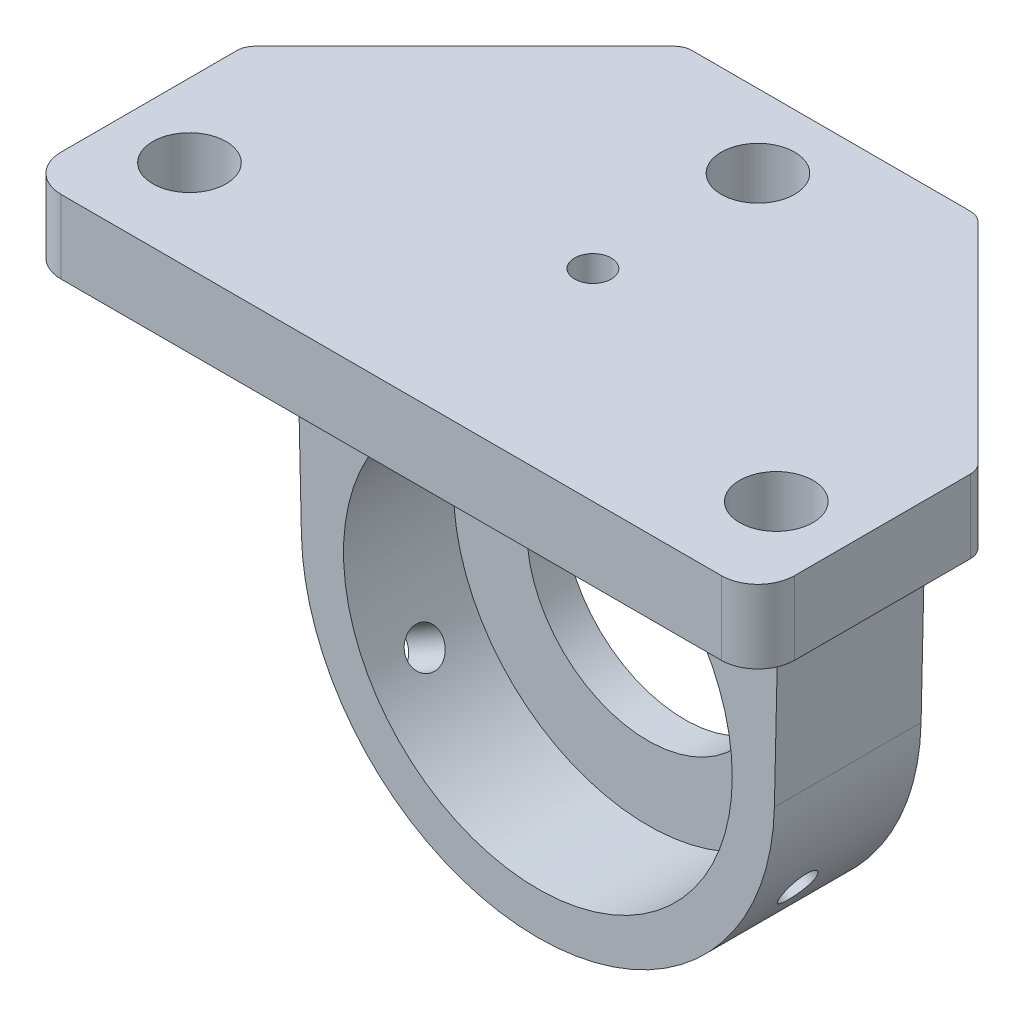
SolidWorks part; units mm, degrees
material "Delrin 2700 NC010, Low Viscosity Acetal Copolymer (SS)"
ref_plane "Front Plane" through (0, 0, 0) normal (0, 0, 1) x (1, 0, 0)
ref_plane "Top Plane" through (0, 0, 0) normal (0, 1, 0) x (1, 0, 0)
ref_plane "Right Plane" through (0, 0, 0) normal (1, 0, 0) x (0, 0, -1)
sketch "Sketch1" plane through (0, 0, 0) normal (0, 1, 0) x (1, 0, 0)
  line L1 (-57.15, 38.1) -> (57.15, 38.1)
  line L2 (-63.5, 31.75) -> (-63.5, -31.75)
  line L3 (-57.15, -38.1) -> (57.15, -38.1)
  line L4 (63.5, 31.75) -> (63.5, -31.75)
  line L5 (-63.5, 38.1) -> (63.5, -38.1) construction
  line L6 (-63.5, -38.1) -> (63.5, 38.1) construction
  arc A0 (57.15, -38.1) -> (63.5, -31.75) centre (57.15, -31.75) ccw
  arc A1 (57.15, 38.1) -> (63.5, 31.75) centre (57.15, 31.75) cw
  arc A2 (-57.15, 38.1) -> (-63.5, 31.75) centre (-57.15, 31.75) ccw
  arc A3 (-63.5, -31.75) -> (-57.15, -38.1) centre (-57.15, -31.75) ccw
  point P0 (0, 0)
  dimension "D3" = 6.35
  dimension "D1" = 76.2
  dimension "D2" = 127
extrude "Boss-Extrude1" add sketch "Sketch1" against normal blind 12.7
sketch "Sketch3" plane through (0, -12.7, 0) normal (0, -1, 0) x (1, 0, 0)
  line L0 (-63.5, -31.75) -> (-63.5, 31.75) construction
  line L1 (-57.15, 38.1) -> (57.15, 38.1) construction
  line L2 (0, 38.1) -> (0, -38.1) construction
  line L3 (57.15, -38.1) -> (-57.15, -38.1) construction
  line L4 (-63.5, 0) -> (63.5, 0) construction
  line L5 (63.5, 31.75) -> (63.5, -31.75) construction
  circle A0 centre (-50.8, 22.225) radius 6.35
  circle A1 centre (50.8, 22.225) radius 6.35
  circle A4 centre (0, -25.4) radius 6.35
  dimension "D1" = 12.7
  dimension "D4" = 12.7
  dimension "D2" = 12.7
  dimension "D3" = 15.875
extrude "Cut-Extrude1" cut sketch "Sketch3" against normal through all
sketch "Sketch2" plane through (0, 0, 0) normal (0, 0, 1) x (1, 0, 0)
  line L0 (0, 0) -> (0, -54.61) construction
  line L1 (-41.91, -12.7) -> (-40.9472, -55.5305)
  line L2 (-57.15, -12.7) -> (57.15, -12.7) construction
  line L3 (41.91, -12.7) -> (40.9472, -55.5305)
  line L4 (-63.5, -12.7) -> (-63.5, 0) construction
  line L5 (63.5, -12.7) -> (63.5, 0) construction
  line L6 (-41.91, -12.7) -> (41.91, -12.7)
  circle A0 centre (0, -54.61) radius 33.3375 construction
  circle A1 centre (0, -54.61) radius 19.05 construction
  arc A2 (-40.9472, -55.5305) -> (40.9472, -55.5305) centre (0, -54.61) ccw
  circle A4 centre (0, -54.61) radius 40.9575 construction
  point P18 (35.56, -54.61)
  dimension "D3" = 38.1
  dimension "D2" = 66.675
  dimension "D1" = 54.61
  dimension "D5" = 21.59
  dimension "D6" = 21.59
  dimension "D4" = 7.62
extrude "Boss-Extrude2" add sketch "Sketch2" along normal mid plane 25.4
sketch "Bearing Reference Geometry" plane through (0, 0, 12.7) normal (0, 0, 1) x (1, 0, 0)
  circle A0 centre (0, -54.61) radius 33.3375
  circle A1 centre (0, -54.61) radius 19.05
  arc A3 (-40.9472, -55.5305) -> (40.9472, -55.5305) centre (0, -54.61) ccw construction
  point P3 (0, -52.9618)
  dimension "D2" = 38.1
  dimension "D1" = 66.675
sketch "Sketch5" plane through (0, 0, 12.7) normal (0, 0, 1) x (1, 0, 0)
  circle A0 centre (0, -54.61) radius 33.655
  dimension "D1" = 67.31
extrude "Cut-Extrude2" cut sketch "Sketch5" against normal through all
sketch "Sketch6" plane through (0, 0, -12.7) normal (0, 0, -1) x (-1, 0, 0)
  circle A0 centre (0, -54.61) radius 33.655 construction
  circle A1 centre (0, -54.61) radius 33.655
  circle A2 centre (0, -54.61) radius 20.955
  dimension "D1" = 12.7
extrude "Boss-Extrude3" add sketch "Sketch6" against normal blind 6.35
ref_axis "Axis1" through (0, -54.61, -6.35) along (0, 0, 1)
sketch "Sketch7" plane through (0, 0, 0) normal (0, 1, 0) x (1, 0, 0)
  line L0 (-33.655, 6.35) -> (33.655, 6.35) construction
  line L1 (-33.655, 6.35) -> (33.655, 6.35) construction
  line L2 (-33.655, -12.7) -> (33.655, -12.7) construction
  line L3 (-33.655, -12.7) -> (33.655, -12.7) construction
  line L4 (-33.655, -3.175) -> (33.655, -3.175) construction
  circle A0 centre (0, -3.175) radius 3.175
  point P3 (0, 0)
  point P10 (-42.5215, -3.175)
  point P11 (5.9089, -3.175)
  point P12 (0, 0)
  dimension "D1" = 6.35
extrude "Cut-Extrude3" cut sketch "Sketch7" against normal up to next
pattern_circular "CirPattern1" count 3 over 360 about axis through (0, -54.61, 12.7) along (0, 0, 1) of "Cut-Extrude3"
sketch "Sketch8" plane through (0, -12.7, 0) normal (0, -1, 0) x (1, 0, 0)
  line L0 (-63.5, 0) -> (-25.4, -38.1)
  line L1 (-63.5, -31.75) -> (-63.5, 31.75) construction
  line L2 (57.15, -38.1) -> (-57.15, -38.1) construction
  line L3 (0, 38.1) -> (0, -38.1) construction
  line L4 (-57.15, 38.1) -> (57.15, 38.1) construction
  line L5 (57.15, -38.1) -> (25.4, -38.1)
  line L6 (-63.5, -31.75) -> (-63.5, 0)
  line L7 (63.5, 31.75) -> (63.5, -31.75) construction
  line L8 (63.5, 0) -> (63.5, -31.75)
  line L9 (63.5, 0) -> (25.4, -38.1)
  line L10 (-25.4, -38.1) -> (-57.15, -38.1)
  arc A0 (-63.5, -31.75) -> (-57.15, -38.1) centre (-57.15, -31.75) ccw construction
  arc A1 (-63.5, -31.75) -> (-57.15, -38.1) centre (-57.15, -31.75) ccw
  arc A2 (57.15, -38.1) -> (63.5, -31.75) centre (57.15, -31.75) ccw construction
  arc A3 (57.15, -38.1) -> (63.5, -31.75) centre (57.15, -31.75) ccw
  dimension "D1" = 45
extrude "Cut-Extrude4" cut sketch "Sketch8" against normal through all
fillet "Fillet1" radius 3.175 8 edges at (0, -12.7, -12.7) (-41.91, -12.7, 0) (41.91, -12.7, 0) (0, -12.7, 12.7) (63.5, -6.35, 0) (-63.5, -6.35, 0) (25.4, -6.35, -38.1) (-25.4, -6.35, -38.1)
equation "\"Bearing Outer Diameter\"= 2.625in"
equation "\"Bearing Holding Lip Thickness\"= 0.5in"
equation "\"Plate Thickness\"= 0.5in"
equation "\"Plate Height\"= 3in"
equation "\"Plate Width\"= 5in"
equation "\"D1@Sketch1\"=\"Plate Height\""
equation "\"D2@Sketch1\"=\"Plate Width\""
equation "\"D1@Boss-Extrude1\"=\"Plate Thickness\""
equation "\"D2@Sketch2\"=\"Bearing Outer Diameter\""
equation "\"D1@Bearing Reference Geometry\"=\"Bearing Outer Diameter\""
equation "\"D1@Sketch6\"=\"Bearing Holding Lip Thickness\""
